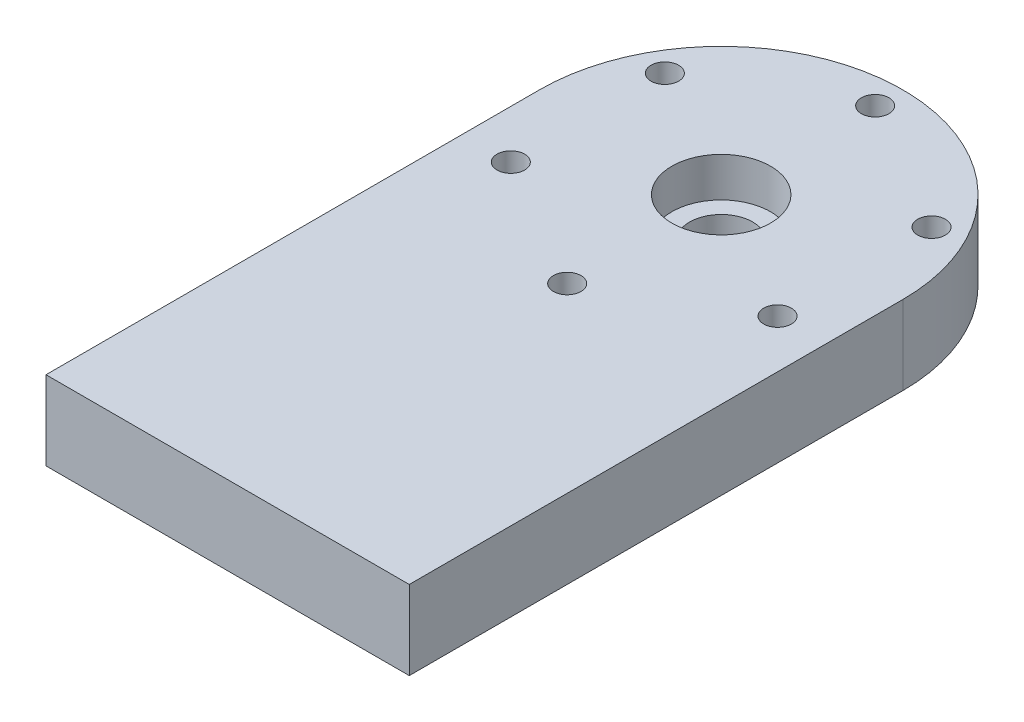
SolidWorks part; units mm, degrees
ref_plane "Front Plane" through (0, 0, 0) normal (0, 0, 1) x (1, 0, 0)
ref_plane "Top Plane" through (0, 0, 0) normal (0, 1, 0) x (1, 0, 0)
ref_plane "Right Plane" through (0, 0, 0) normal (1, 0, 0) x (0, 0, -1)
sketch "Sketch3" plane through (0, 0, 0) normal (0, 1, 0) x (1, 0, 0)
  line L1 (0, 0) -> (184, 0)
  line L2 (0, 0) -> (0, 250)
  line L3 (0, 250) -> (184, 250) construction
  line L4 (184, 0) -> (184, 250)
  arc A0 (184, 250) -> (0, 250) centre (92, 250) ccw
  circle A1 centre (92, 250) radius 78 construction
  dimension "D3" = 156
  dimension "D1" = 250
  dimension "D2" = 184
extrude "Boss-Extrude1" add sketch "Sketch3" along normal blind 40
sketch "Sketch5" plane through (0, 40, 0) normal (0, 1, 0) x (1, 0, 0)
  circle A0 centre (92, 250) radius 25
  dimension "D1" = 50
extrude "Cut-Extrude1" cut sketch "Sketch5" against normal blind 20
sketch "Sketch6" plane through (0, 0, 0) normal (0, -1, 0) x (1, 0, 0)
  circle A0 centre (92, -250) radius 16
  dimension "D1" = 32
extrude "Cut-Extrude2" cut sketch "Sketch6" against normal blind 20
sketch "Sketch7" plane through (0, 40, 0) normal (0, 1, 0) x (1, 0, 0)
  circle A0 centre (92, 250) radius 78 construction
  circle A1 centre (92, 328) radius 7
  dimension "D1" = 156
  dimension "D2" = 14
extrude "Cut-Extrude3" cut sketch "Sketch7" against normal blind 25
pattern_circular "CirPattern1" count 6 over 360 about axis through (92, 40, -250) along (0, 1, 0) of "Cut-Extrude3"
sketch "Sketch8" plane through (0, 0, 0) normal (0, -1, 0) x (1, 0, 0)
  circle A0 centre (92, -250) radius 78 construction
  circle A1 centre (92, -328) radius 12
  dimension "D1" = 156
  dimension "D2" = 24
extrude "Cut-Extrude4" cut sketch "Sketch8" against normal blind 15
pattern_circular "CirPattern2" count 6 over 360 about axis through (92, 0, -250) along (0, 1, 0) of "Cut-Extrude4"
